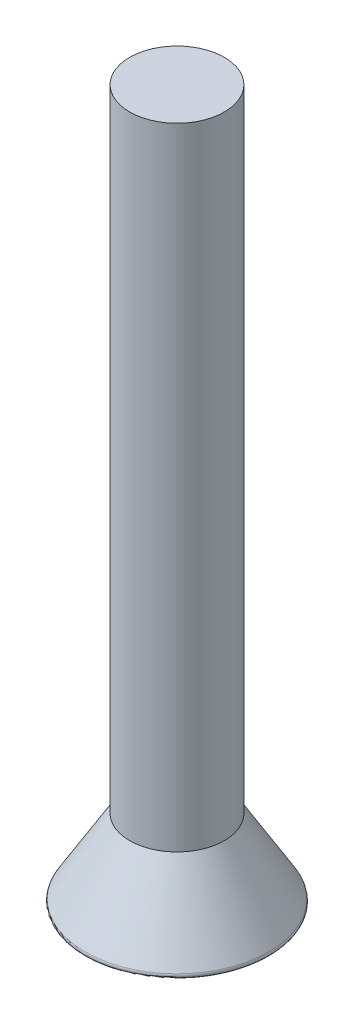
SolidWorks part; units mm, degrees
ref_plane "Front Plane" through (0, 0, 0) normal (0, 0, 1) x (1, 0, 0)
ref_plane "Top Plane" through (0, 0, 0) normal (0, 1, 0) x (1, 0, 0)
ref_plane "Right Plane" through (0, 0, 0) normal (1, 0, 0) x (0, 0, -1)
sketch "Sketch1" plane through (0, 0, 0) normal (0, 1, 0) x (1, 0, 0)
  circle A0 centre (0, 0) radius 3
  dimension "D1" = 6
extrude "Boss-Extrude1" add sketch "Sketch1" along normal blind 2.5
sketch "Sketch2" plane through (0, 2.5, 0) normal (0, 1, 0) x (1, 0, 0)
  circle A0 centre (0, 0) radius 1.5
  dimension "D1" = 3
extrude "Boss-Extrude2" add sketch "Sketch2" along normal blind 20
chamfer "Chamfer1" distance 2.5 distance2 1.5 1 edges at (0, 2.5, 3) first distance on face at (0, 2.5, 3)
fillet "Fillet1" radius 0.1 1 edges at (0, 0, 3)
sketch "Sketch3" plane through (0, 0, 0) normal (0, -1, 0) x (1, 0, 0)
  line L1 (0.5, 1.5) -> (-0.5, 1.5)
  line L2 (0.5, 1.5) -> (0.5, -1.5)
  line L3 (0.5, -1.5) -> (-0.5, -1.5)
  line L4 (-0.5, 1.5) -> (-0.5, -1.5)
  line L5 (0.5, 1.5) -> (-0.5, -1.5) construction
  line L6 (0.5, -1.5) -> (-0.5, 1.5) construction
  line L7 (1.5, 0.5) -> (-1.5, 0.5)
  line L8 (1.5, 0.5) -> (1.5, -0.5)
  line L9 (1.5, -0.5) -> (-1.5, -0.5)
  line L10 (-1.5, 0.5) -> (-1.5, -0.5)
  line L11 (1.5, 0.5) -> (-1.5, -0.5) construction
  line L12 (1.5, -0.5) -> (-1.5, 0.5) construction
  point P0 (0, 0)
  point P6 (0, 0)
  dimension "D1" = 3
  dimension "D2" = 1
  dimension "D3" = 1
  dimension "D4" = 3
extrude "Cut-Extrude2" cut sketch "Sketch3" against normal blind 1.5 contours L2 L9 L4 L3 | L7 L10 L9 L4 | L9 L2 L7 L4 | L7 L2 L1 L4 | L9 L8 L7 L2 region at (0, 0, 1) region at (1, 0, 0) region at (0, 0, 0) region at (-1, 0, 0) region at (0, 0, -1)
chamfer "Chamfer7" distance 0.3 distance2 1.5 12 edges at (0, 1.5, -1.5) (0, 1.5, 1.5) (0.5, 1.5, 1) (1, 1.5, 0.5) (-0.5, 1.5, 1) (-1, 1.5, 0.5) (-1.5, 1.5, 0) (1.5, 1.5, 0) (1, 1.5, -0.5) (0.5, 1.5, -1) (-1, 1.5, -0.5) (-0.5, 1.5, -1) first distance on face at (0, 1.5, 0)
